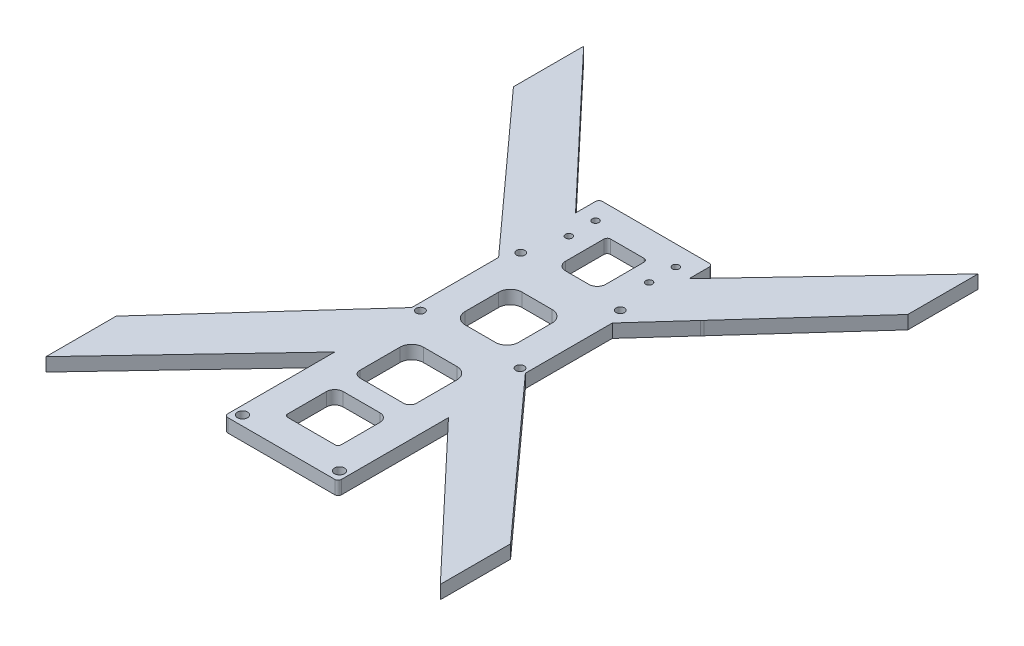
SolidWorks part; units mm, degrees
ref_plane "Front Plane" through (0, 0, 0) normal (0, 0, 1) x (1, 0, 0)
ref_plane "Top Plane" through (0, 0, 0) normal (0, 1, 0) x (1, 0, 0)
ref_plane "Right Plane" through (0, 0, 0) normal (1, 0, 0) x (0, 0, -1)
sketch "Frame Sketch" plane through (0, 0, 0) normal (0, 1, 0) x (1, 0, 0)
  line L0 (6.2981, 0.1404) -> (6.2981, 126.6085) construction
  line L6 (-48.6747, 0) -> (67.0859, 0) construction
  line L11 (6.2981, 0.1404) -> (6.2981, -105.8001) construction
  line L23 (-9.7019, 56.1404) -> (22.2981, 56.1404)
  line L24 (-10.7019, 55.1404) -> (-10.7019, -54.8596)
  line L25 (-9.7019, -55.8596) -> (22.2981, -55.8596)
  line L26 (23.2981, 55.1404) -> (23.2981, -54.8596)
  line L27 (-10.7019, 56.1404) -> (23.2981, -55.8596) construction
  line L28 (-10.7019, -55.8596) -> (23.2981, 56.1404) construction
  line L34 (23.2981, -22.8596) -> (65.2709, -67.262)
  line L37 (65.2709, -46.262) -> (65.2709, -67.262)
  line L38 (23.2981, 0.1404) -> (65.2709, -46.262)
  line L43 (23.2981, -22.8596) -> (23.2981, 0.1404)
  line L44 (-0.8423, -46.8596) -> (13.4385, -46.8596)
  line L45 (-1.7019, -46) -> (-1.7019, -34.3596)
  line L46 (0.7981, -31.8596) -> (11.7981, -31.8596)
  line L47 (14.2981, -46) -> (14.2981, -34.3596)
  line L48 (-1.7019, -46.8596) -> (14.2981, -31.8596) construction
  line L49 (-1.7019, -31.8596) -> (14.2981, -46.8596) construction
  line L50 (12.7981, -25.8596) -> (-0.2019, -25.8596)
  line L51 (14.7981, -23.8596) -> (14.7981, -11.8596)
  line L52 (11.2981, -8.3596) -> (1.2981, -8.3596)
  line L53 (-2.2019, -23.8596) -> (-2.2019, -11.8596)
  line L54 (14.7981, -25.8596) -> (-2.2019, -8.3596) construction
  line L55 (14.7981, -8.3596) -> (-2.2019, -25.8596) construction
  line L56 (1.7981, 3.6404) -> (10.7981, 3.6404)
  line L57 (-1.7019, 7.1404) -> (-1.7019, 17.1404)
  line L58 (1.7981, 20.6404) -> (10.7981, 20.6404)
  line L59 (14.2981, 7.1404) -> (14.2981, 17.1404)
  line L60 (-1.7019, 3.6404) -> (14.2981, 20.6404) construction
  line L61 (-1.7019, 20.6404) -> (14.2981, 3.6404) construction
  line L62 (2.7981, 32.6404) -> (9.7981, 32.6404)
  line L63 (0.2981, 35.1404) -> (0.2981, 46.6404)
  line L64 (1.2981, 47.6404) -> (11.2981, 47.6404)
  line L65 (12.2981, 35.1404) -> (12.2981, 46.6404)
  line L66 (0.2981, 32.6404) -> (12.2981, 47.6404) construction
  line L67 (0.2981, 47.6404) -> (12.2981, 32.6404) construction
  line L69 (23.2981, 49.1404) -> (65.2709, 93.5427)
  line L70 (23.2981, 26.1404) -> (65.2709, 72.5427)
  line L71 (65.2709, 72.5427) -> (65.2709, 93.5427)
  line L72 (23.2981, 26.1404) -> (23.2981, 49.1404)
  line L73 (-10.7019, 26.1404) -> (-52.6747, 72.5427)
  line L74 (-52.6747, 72.5427) -> (-52.6747, 93.5427)
  line L75 (-10.7019, 49.1404) -> (-52.6747, 93.5427)
  line L76 (-10.7019, 26.1404) -> (-10.7019, 49.1404)
  line L77 (-10.7019, -22.8596) -> (-52.6747, -67.262)
  line L78 (-52.6747, -46.262) -> (-52.6747, -67.262)
  line L79 (-10.7019, 0.1404) -> (-52.6747, -46.262)
  line L80 (-10.7019, -22.8596) -> (-10.7019, 0.1404)
  line L81 (-23.7019, 40.5123) -> (-10.7019, 26.1404)
  line L82 (-10.7019, 0.1404) -> (-23.7019, -14.2315)
  line L83 (-23.7019, 40.5123) -> (-10.7019, 26.1404)
  line L84 (-10.7019, 0.1404) -> (-23.7019, -14.2315)
  line L85 (-23.7019, 40.5123) -> (-10.7019, 26.1404)
  line L86 (-10.7019, 0.1404) -> (-23.7019, -14.2315)
  line L87 (-23.7019, 40.5123) -> (-10.7019, 26.1404)
  line L88 (-38.2482, 15.6404) -> (41.3847, 15.6404) construction
  line L89 (-10.7019, 40.5123) -> (-10.7019, -14.2315)
  arc A8 (23.2981, 55.1404) -> (22.2981, 56.1404) centre (22.2981, 55.1404) ccw
  arc A9 (23.2981, -54.8596) -> (22.2981, -55.8596) centre (22.2981, -54.8596) cw
  arc A10 (-9.7019, 56.1404) -> (-10.7019, 55.1404) centre (-9.7019, 55.1404) ccw
  arc A11 (-9.7019, -55.8596) -> (-10.7019, -54.8596) centre (-9.7019, -54.8596) cw
  circle A12 centre (-8.2019, -52.9596) radius 1.5
  circle A13 centre (20.7981, -52.9596) radius 1.5
  arc A14 (14.2981, -46) -> (13.4385, -46.8596) centre (13.4385, -46) cw
  arc A15 (-0.8423, -46.8596) -> (-1.7019, -46) centre (-0.8423, -46) cw
  arc A16 (-1.7019, -34.3596) -> (0.7981, -31.8596) centre (0.7981, -34.3596) cw
  arc A17 (11.7981, -31.8596) -> (14.2981, -34.3596) centre (11.7981, -34.3596) cw
  arc A18 (14.7981, -23.8596) -> (12.7981, -25.8596) centre (12.7981, -23.8596) cw
  arc A19 (-2.2019, -23.8596) -> (-0.2019, -25.8596) centre (-0.2019, -23.8596) ccw
  arc A20 (14.7981, -11.8596) -> (11.2981, -8.3596) centre (11.2981, -11.8596) ccw
  arc A21 (1.2981, -8.3596) -> (-2.2019, -11.8596) centre (1.2981, -11.8596) ccw
  arc A22 (1.7981, 3.6404) -> (-1.7019, 7.1404) centre (1.7981, 7.1404) cw
  arc A23 (14.2981, 7.1404) -> (10.7981, 3.6404) centre (10.7981, 7.1404) cw
  arc A24 (1.7981, 20.6404) -> (-1.7019, 17.1404) centre (1.7981, 17.1404) ccw
  arc A25 (14.2981, 17.1404) -> (10.7981, 20.6404) centre (10.7981, 17.1404) ccw
  arc A26 (2.7981, 32.6404) -> (0.2981, 35.1404) centre (2.7981, 35.1404) cw
  arc A27 (12.2981, 35.1404) -> (9.7981, 32.6404) centre (9.7981, 35.1404) cw
  arc A28 (1.2981, 47.6404) -> (0.2981, 46.6404) centre (1.2981, 46.6404) ccw
  arc A29 (12.2981, 46.6404) -> (11.2981, 47.6404) centre (11.2981, 46.6404) ccw
  circle A30 centre (18.2981, 50.1404) radius 1
  circle A31 centre (18.2981, 42.1404) radius 1
  circle A32 centre (-5.7019, 50.1404) radius 1
  circle A33 centre (-5.7019, 42.1404) radius 1
  circle A34 centre (-8.6019, 30.6404) radius 1.25
  circle A35 centre (-8.6019, 0.6404) radius 1.25
  circle A36 centre (21.1981, 0.6404) radius 1.25
  circle A37 centre (21.1981, 30.6404) radius 1.25
  circle A39 centre (-59.8607, 83.0427) radius 12.7235
  circle A40 centre (-59.8607, 83.0427) radius 3.5
  spline S0 degree 3 poles (-23.7019, 40.5123) (-9.7905, 25.4071) (-9.7035, 0.8596) (-23.7019, -14.2315) knots 0 0 0 0 1 1 1 1
  spline S1 degree 3 poles (36.2981, 40.5123) (22.3867, 25.4071) (22.2997, 0.8596) (36.2981, -14.2315) knots 0 0 0 0 1 1 1 1
  point P0 (0, 0)
  point P6 (0, 0)
  point P52 (6.2981, -39.3596)
  point P69 (6.2981, -17.1096)
  point P86 (6.2981, 12.1404)
  point P103 (6.2981, 40.1404)
  dimension "D6" = 1
  dimension "D7" = 2.9
  dimension "D8" = 2.5
  dimension "D5" = 17.5
  dimension "D11" = 9
  dimension "D12" = 9
  dimension "D13" = 12
  dimension "D14" = 33
  dimension "D17" = 23
  dimension "D18" = 21
  dimension "D19" = 26
  dimension "D20" = 7
  dimension "D23" = 23
  dimension "D24" = 21
  dimension "D25" = 1
  dimension "D26" = 23
  dimension "D30" = 6
  dimension "D31" = 6
  dimension "D32" = 8
  dimension "D33" = 15
  dimension "D34" = 7
  dimension "D36" = 2.5
  dimension "D37" = 4.5
  dimension "D38" = 2.1
  dimension "D3" = 112
  dimension "D4" = 34
  dimension "D9" = 15
  dimension "D10" = 16
  dimension "D15" = 17
  dimension "D16" = 6
  dimension "D21" = 17
  dimension "D22" = 16
  dimension "D27" = 12
  dimension "D28" = 15
  dimension "D29" = 12
  dimension "D35" = 13
extrude "Frame Bottom Plate" add sketch "Frame Sketch" along normal blind 4 contours L26 L23 L24 L25 | L37 | L70 L71 L69 L26 | L24 L79 L78 L77 | L34 L37 L38 L43 | L73 L74 L75 L76 region at (6.2981, 0, -1.5918) region at (43.9665, 0, -59.9976) region at (-31.3704, 0, 33.7169)
